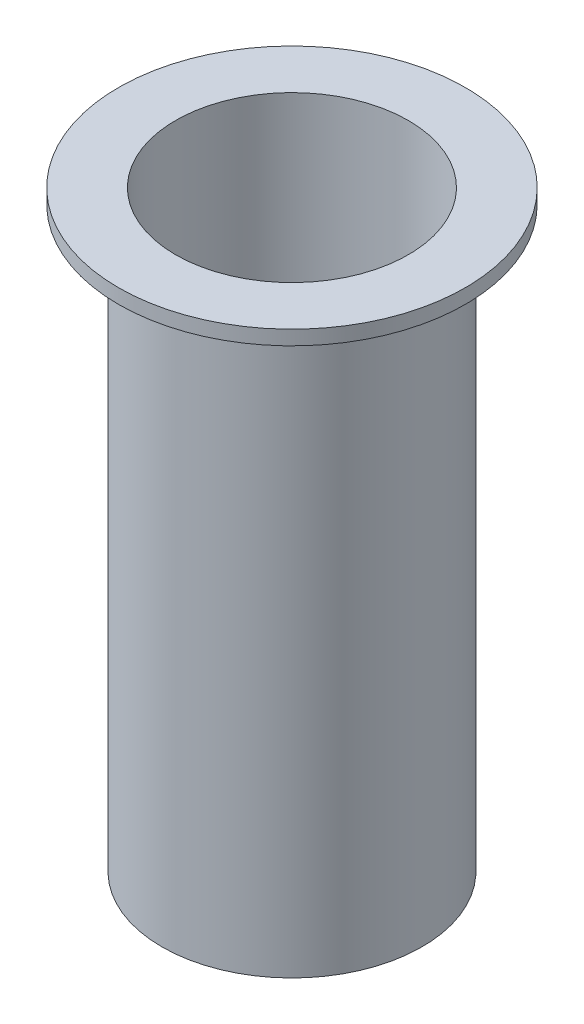
SolidWorks part; units mm, degrees
ref_plane "Front Plane" through (0, 0, 0) normal (0, 0, 1) x (1, 0, 0)
ref_plane "Top Plane" through (0, 0, 0) normal (0, 1, 0) x (1, 0, 0)
ref_plane "Right Plane" through (0, 0, 0) normal (1, 0, 0) x (0, 0, -1)
ref_axis "Axial" through (0, 55, 0) along (0, -1, 0)
sketch "Sketch1" plane through (0, 0, 0) normal (0, 1, 0) x (1, 0, 0)
  circle A0 centre (0, 0) radius 51.1302
  circle A1 centre (0, 0) radius 57.15
  dimension "D1" = 114.3
  dimension "D2" = 102.2604
extrude "Scheduled Chamber" add sketch "Sketch1" against normal blind 260.35
sketch "Sketch2" plane through (0, 0, 0) normal (0, 1, 0) x (1, 0, 0)
  circle A0 centre (0, 0) radius 54.102
  circle A1 centre (0, 0) radius 76.2
  dimension "D1" = 152.4
  dimension "D2" = 108.204
extrude "Flange" add sketch "Sketch2" against normal blind 6.35
